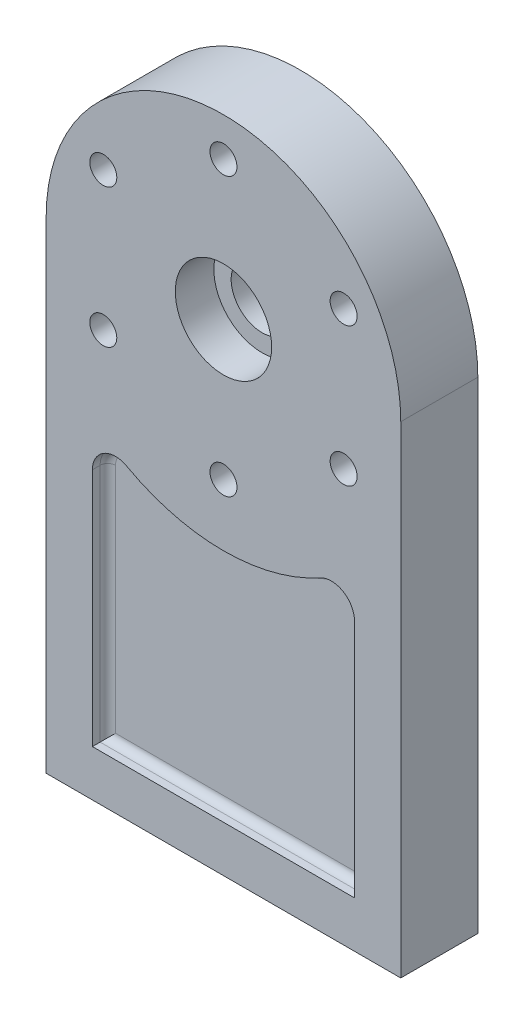
SolidWorks part; units mm, degrees
ref_plane "Front Plane" through (0, 0, 0) normal (0, 0, 1) x (1, 0, 0)
ref_plane "Top Plane" through (0, 0, 0) normal (0, 1, 0) x (1, 0, 0)
ref_plane "Right Plane" through (0, 0, 0) normal (1, 0, 0) x (0, 0, -1)
sketch "Sketch1" plane through (0, 0, 0) normal (0, 0, 1) x (1, 0, 0)
  line L0 (46, 125) -> (46, 0)
  line L1 (46, 0) -> (-46, 0)
  line L2 (-46, 0) -> (-46, 125)
  arc A0 (46, 125) -> (-46, 125) centre (0, 125) ccw
  circle A1 centre (0, 125) radius 8
  dimension "D1" = 125
  dimension "D2" = 92
  dimension "D3" = 16
extrude "Boss-Extrude1" add sketch "Sketch1" along normal mid plane 20
sketch "Sketch3" plane through (0, 0, 10) normal (0, 0, 1) x (1, 0, 0)
  circle A0 centre (0, 125) radius 12.5
  dimension "D1" = 25
extrude "Cut-Extrude1" cut sketch "Sketch3" against normal blind 10
sketch "Sketch4" plane through (0, 0, 10) normal (0, 0, 1) x (1, 0, 0)
  circle A0 centre (0, 161) radius 3.5
  circle A1 centre (0, 125) radius 36 construction
  dimension "D1" = 72
  dimension "D2" = 7
extrude "Cut-Extrude2" cut sketch "Sketch4" against normal through all
hole_wizard "Tap Drill for M10x1.25 Tap1" positions "Sketch6" profile "Sketch7" hole size "M10x1.25" standard "ISO"
sketch "Sketch6" plane through (0, 0, 0) normal (0, -1, 0) x (-1, 0, 0)
  line L0 (46, -10) -> (-46, -10) construction
  line L1 (-46, -10) -> (-46, 10) construction
  point P0 (-30, 0)
  point P2 (30, 0)
  dimension "D1" = 10
  dimension "D2" = 16
  dimension "D3" = 60
sketch "Sketch7" plane through (30, 0, 0) normal (1, 0, 0) x (0, 0, -1)
  line L0 (0, 0) -> (0, 26.6438)
  line L1 (0, 26.6438) -> (4.4, 24)
  line L2 (4.4, 24) -> (4.4, 0.025)
  line L3 (4.4, 0.025) -> (4.425, 0)
  line L5 (4.425, 0) -> (0, 0)
  line L6 (-4.4, 0.025) -> (-4.425, 0) construction
  line L10 (0, 26.6438) -> (-4.4, 24) construction
  line L11 (0, -6.35) -> (0, 107.95) construction
  dimension "Hole Dia." = 8.8
  dimension "Hole Depth" = 24
  dimension "Near C'Sink Dia." = 8.85
  dimension "Near C'Sink Angle" = 90
  dimension "Drill Angle" = 118
sketch "Sketch8" plane through (0, 0, 10) normal (0, 0, 1) x (1, 0, 0)
  line L9 (-34, 125) -> (-34, 12)
  line L10 (-34, 12) -> (34, 12)
  line L11 (34, 12) -> (34, 125)
  line L12 (-34, 74.2063) -> (-34, 12)
  line L13 (-34, 12) -> (34, 12)
  line L14 (34, 12) -> (34, 74.2063)
  arc A0 (-25.1034, 79.4608) -> (25.1034, 79.4608) centre (0, 125) ccw
  arc A1 (25.1034, 79.4608) -> (34, 74.2063) centre (28, 74.2063) cw
  arc A2 (-25.1034, 79.4608) -> (-34, 74.2063) centre (-28, 74.2063) ccw
  dimension "D1" = 104
  dimension "D3" = 6
  dimension "D2" = 12
extrude "Cut-Extrude4" cut sketch "Sketch8" against normal blind 4
fillet "Fillet1" radius 2 6 edges at (34, 43.1031, 6) (0, 12, 6) (-34, 43.1031, 6) (-31.0513, 79.3725, 6) (0, 73, 6) (31.0513, 79.3725, 6)
mirror "Mirror1" about plane through (0, 0, 0) normal (0, 0, 1) of "Cut-Extrude4", "Fillet1"
sketch "Sketch9" plane through (0, 0, -10) normal (0, 0, -1) x (-1, 0, 0)
  circle A0 centre (0, 161) radius 6
  dimension "D1" = 12
extrude "Cut-Extrude5" cut sketch "Sketch9" against normal blind 6
pattern_circular "CirPattern1" count 6 over 360 about axis through (0, 125, -10) along (0, 0, 1) of "Cut-Extrude5", "Cut-Extrude2"
